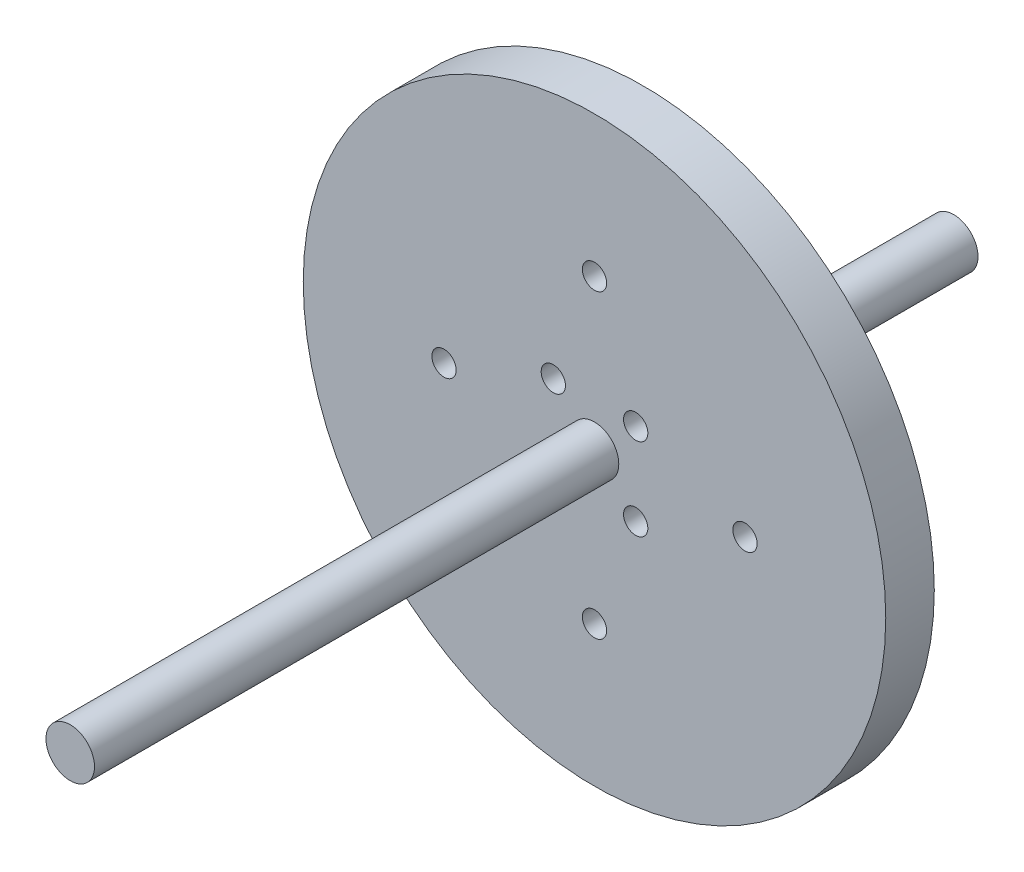
SolidWorks part; units mm, degrees
ref_plane "Front Plane" through (0, 0, 0) normal (0, 0, 1) x (1, 0, 0)
ref_plane "Top Plane" through (0, 0, 0) normal (0, 1, 0) x (1, 0, 0)
ref_plane "Right Plane" through (0, 0, 0) normal (1, 0, 0) x (0, 0, -1)
sketch "Sketch1" plane through (0, 0, 0) normal (0, 0, 1) x (1, 0, 0)
  circle A0 centre (0, 0) radius 30
extrude "Boss-Extrude1" add sketch "Sketch1" along normal blind 5
sketch "Sketch2" plane through (0, 0, 5) normal (0, 0, 1) x (1, 0, 0)
  line L0 (0, 15.5) -> (0, 0) construction
  line L1 (0, 0) -> (4.2426, 4.2426) construction
  circle A0 centre (0, 15.5) radius 1.25
  circle A1 centre (15.5, 0) radius 1.25
  circle A2 centre (0, -15.5) radius 1.25
  circle A3 centre (-15.5, 0) radius 1.25
  circle A4 centre (4.2426, 4.2426) radius 1.25
  circle A5 centre (4.2426, -4.2426) radius 1.25
  circle A6 centre (-4.2426, -4.2426) radius 1.25
  circle A7 centre (-4.2426, 4.2426) radius 1.25
  point P12 (0, 0)
  point P21 (0, 0)
  dimension "D1" = 15.5
  dimension "D3" = 2.5
  dimension "D4" = 2.5
  dimension "D5" = 6
  dimension "D7" = 45
  dimension "D2" = 4
  dimension "D6" = 4
extrude "Cut-Extrude1" cut sketch "Sketch2" against normal blind 5
sketch "Sketch3" plane through (0, 0, 0) normal (0, 0, -1) x (-1, 0, 0)
  circle A0 centre (0, 0) radius 2.5
extrude "Boss-Extrude2" add sketch "Sketch3" along normal blind 32
sketch "Sketch4" plane through (0, 0, 5) normal (0, 0, 1) x (1, 0, 0)
  circle A0 centre (0, 0) radius 2.5
extrude "Boss-Extrude3" add sketch "Sketch4" along normal blind 54
